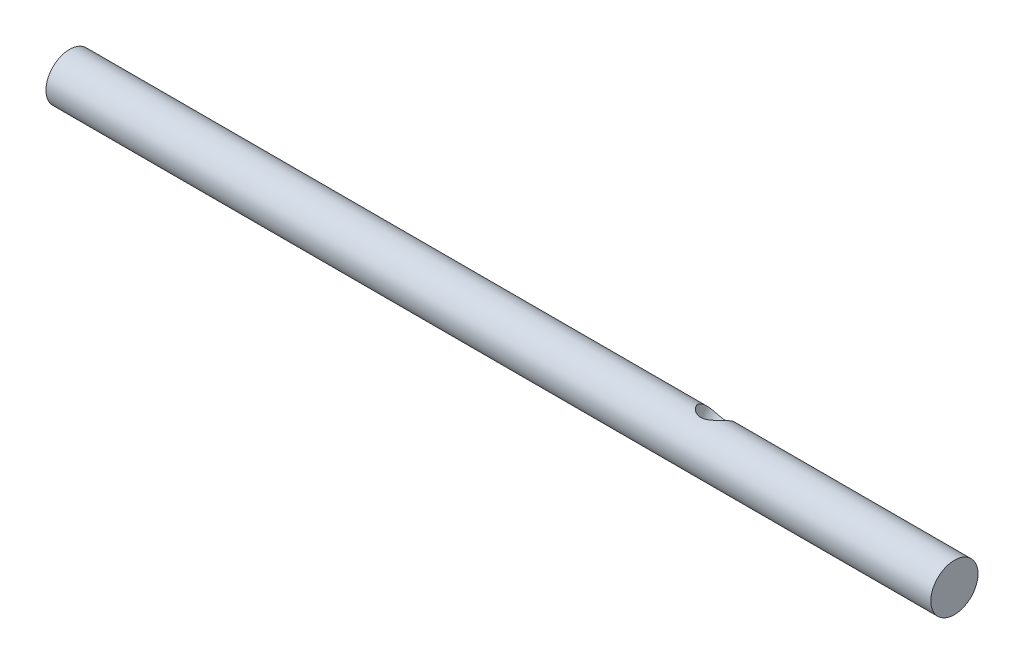
SolidWorks part; units mm, degrees
ref_plane "Front Plane" through (0, 0, 0) normal (0, 0, 1) x (1, 0, 0)
ref_plane "Top Plane" through (0, 0, 0) normal (0, 1, 0) x (1, 0, 0)
ref_plane "Right Plane" through (0, 0, 0) normal (1, 0, 0) x (0, 0, -1)
sketch "Sketch1" plane through (0, 0, 0) normal (1, 0, 0) x (0, 0, -1)
  circle A0 centre (0, 0) radius 4
  dimension "D1" = 8
extrude "Boss-Extrude1" add sketch "Sketch1" along normal mid plane 150
sketch "Sketch2" plane through (-1373.6271, 398.0341, -1457.2495) normal (0, -0.8537, 0.5208) x (0, 0.5208, 0.8537)
  line L0 (1036.7375, -1497.7488) -> (1036.7375, -1368.0826) construction
  line L1 (1032.7375, -1448.6271) -> (1040.7375, -1448.6271) construction
  circle A1 centre (1036.7375, -1406.1271) radius 2.5
  dimension "D1" = 5
  dimension "D2" = 42.5
extrude "Cut-Extrude1" cut sketch "Sketch2" along normal blind 1097
